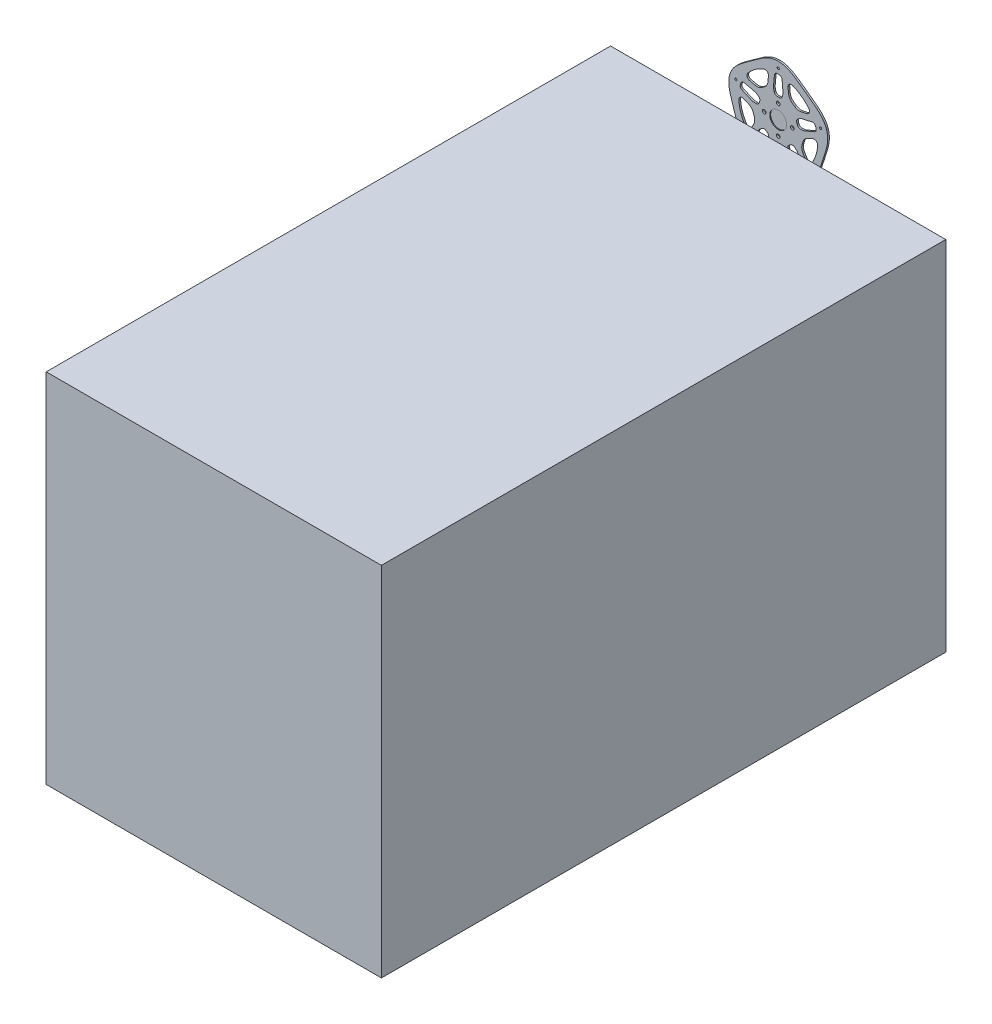
SolidWorks part; units mm, degrees
material "Stop 1060"
ref_plane "Płaszczyzna przednia" through (0, 0, 0) normal (0, 0, 1) x (1, 0, 0)
ref_plane "Płaszczyzna górna" through (0, 0, 0) normal (0, 1, 0) x (1, 0, 0)
ref_plane "Płaszczyzna prawa" through (0, 0, 0) normal (1, 0, 0) x (0, 0, -1)
sketch "Szkic1" plane through (0, 0, 0) normal (0, 0, 1) x (1, 0, 0)
  line L0 (0, 0) -> (51.1373, 70.3845) construction
  line L1 (0, 0) -> (0, 87) construction
  line L42 (64.6668, 37.9895) -> (41.3071, 32.5965)
  line L43 (69.2558, 28.7859) -> (41.6924, 22.4224)
  line L44 (38.6664, 21.1739) -> (30.949, 16.3814)
  line L45 (35.8646, 30.1162) -> (26.2605, 23.1384)
  line L46 (43.7274, 5.5975) -> (34.667, 4.9385)
  line L47 (72.9491, 17.4193) -> (46.9094, 6.3661)
  line L48 (-6.7939, 65.4105) -> (-8.4413, 46.5807)
  line L49 (-8.189, 43.317) -> (-7.2584, 39.5397)
  line L50 (69.805, 5.2211) -> (52.5779, -2.0914)
  line L51 (46.7169, -3.2838) -> (34.8456, -3.2838)
  line L52 (56.1133, -49.7624) -> (43.7657, -29.2126)
  line L53 (-7.4667, 69.6006) -> (-7.4667, 29.102) construction
  line L54 (48.7783, -56.9709) -> (34.2086, -32.7229)
  line L55 (32.0861, -30.2308) -> (25.1434, -24.3721)
  line L56 (39.725, -24.8029) -> (30.1209, -17.8251)
  line L57 (-17.3877, 59.0596) -> (-18.2365, 49.3583)
  line L58 (18.836, -39.8576) -> (15.4095, -31.4442)
  line L59 (39.1092, -63.9958) -> (20.5503, -42.6462)
  line L60 (26.5365, -64.7751) -> (14.2585, -50.6508)
  line L61 (-17.5594, 43.4157) -> (-13.891, 32.1254)
  line L62 (11.3132, -45.4452) -> (7.6448, -34.1549)
  line L63 (-29.9869, -68.7443) -> (-14.2585, -50.6508)
  line L64 (-39.1092, -63.9958) -> (-20.5503, -42.6462)
  line L65 (-18.836, -39.8576) -> (-15.4095, -31.4442)
  line L66 (-11.3132, -45.4452) -> (-7.6448, -34.1549)
  line L67 (-32.0861, -30.2308) -> (-25.1434, -24.3721)
  line L68 (-48.7783, -56.9709) -> (-34.2086, -32.7229)
  line L69 (-53.4046, -45.2543) -> (-43.7657, -29.2126)
  line L70 (-39.725, -24.8029) -> (-30.1209, -17.8251)
  line L71 (-74.6462, 7.2761) -> (-52.5779, -2.0914)
  line L72 (-72.9491, 17.4193) -> (-46.9094, 6.3661)
  line L73 (-43.7274, 5.5975) -> (-34.667, 4.9385)
  line L74 (0, 0) -> (32.9395, 101.3773) construction
  line L111 (-46.7169, -3.2838) -> (-34.8456, -3.2838)
  line L112 (-38.6664, 21.1739) -> (-30.949, 16.3814)
  line L113 (-69.2558, 28.7859) -> (-41.6924, 22.4224)
  line L114 (-59.5423, 36.8064) -> (-41.3071, 32.5965)
  line L115 (-35.8646, 30.1162) -> (-26.2605, 23.1384)
  line L116 (-29.0561, 35.0629) -> (-24.3679, 38.469)
  line L117 (24.3679, 38.469) -> (29.0561, 35.0629)
  line L118 (44.1163, -11.2877) -> (42.3256, -16.799)
  line L119 (2.8975, -45.4452) -> (-2.8975, -45.4452)
  line L120 (17.5594, 43.4157) -> (13.891, 32.1254)
  line L121 (8.189, 43.317) -> (7.2584, 39.5397)
  line L122 (16.6054, 68.0019) -> (18.2365, 49.3583)
  line L123 (5.9758, 74.7616) -> (8.4413, 46.5807)
  line L124 (-42.3256, -16.799) -> (-44.1163, -11.2877)
  circle A0 centre (0, 0) radius 79 construction
  circle A2 centre (0, 0) radius 25 construction
  circle A3 centre (0, 0) radius 3.3
  circle A4 centre (0, 25) radius 3.2
  circle A5 centre (0, 79) radius 1.9
  circle A6 centre (25, 0) radius 3.2
  circle A7 centre (0, -25) radius 3.2
  circle A8 centre (-25, 0) radius 3.2
  circle A9 centre (75.1335, 24.4123) radius 1.9
  circle A10 centre (46.435, -63.9123) radius 1.9
  circle A11 centre (-46.435, -63.9123) radius 1.9
  circle A12 centre (-75.1335, 24.4123) radius 1.9
  circle A13 centre (0, 0) radius 87 construction
  arc A54 (35.8646, 30.1162) -> (41.3071, 32.5965) centre (44.6814, 17.9809) cw
  arc A55 (38.6664, 21.1739) -> (41.6924, 22.4224) centre (43.9419, 12.6787) cw
  arc A56 (43.7274, 5.5975) -> (46.9094, 6.3661) centre (43.0021, 15.5711) ccw
  arc A57 (46.7169, -3.2838) -> (52.5779, -2.0914) centre (46.7169, 11.7162) ccw
  arc A58 (39.725, -24.8029) -> (43.7657, -29.2126) centre (30.9082, -36.9381) cw
  arc A59 (32.0861, -30.2308) -> (34.2086, -32.7229) centre (25.6369, -37.8733) cw
  circle A60 centre (0, 0) radius 70
  arc A61 (-8.189, 43.317) -> (-8.4413, 46.5807) centre (1.5207, 45.7091) cw
  arc A62 (18.836, -39.8576) -> (20.5503, -42.6462) centre (28.0974, -36.0857) ccw
  arc A63 (11.3132, -45.4452) -> (14.2585, -50.6508) centre (25.5791, -40.8099) ccw
  arc A64 (-11.3132, -45.4452) -> (-14.2585, -50.6508) centre (-25.5791, -40.8099) cw
  arc A65 (-18.2391, 49.3276) -> (-18.2365, 49.3583) centre (-3.2936, 48.051) cw
  arc A66 (-18.836, -39.8576) -> (-20.5503, -42.6462) centre (-28.0974, -36.0857) cw
  arc A67 (-32.0861, -30.2308) -> (-34.2086, -32.7229) centre (-25.6369, -37.8733) ccw
  arc A68 (-39.725, -24.8029) -> (-43.7657, -29.2126) centre (-30.9082, -36.9381) ccw
  arc A69 (8.189, 43.317) -> (8.4413, 46.5807) centre (-1.5207, 45.7091) ccw
  arc A70 (-46.7169, -3.2838) -> (-52.5779, -2.0914) centre (-46.7169, 11.7162) cw
  arc A71 (-43.7274, 5.5975) -> (-46.9094, 6.3661) centre (-43.0021, 15.5711) cw
  arc A72 (-38.6664, 21.1739) -> (-41.6924, 22.4224) centre (-43.9419, 12.6787) ccw
  arc A73 (17.5594, 43.4157) -> (18.2365, 49.3583) centre (3.2936, 48.051) ccw
  arc A74 (-41.2772, 32.5895) -> (-41.3071, 32.5965) centre (-44.6814, 17.9809) ccw
  arc A75 (-24.3679, 38.469) -> (-18.2391, 49.3276) centre (-33.1847, 50.6043) ccw
  arc A76 (-41.2772, 32.5895) -> (-29.0561, 35.0629) centre (-37.8729, 47.1981) ccw
  arc A77 (29.0561, 35.0629) -> (41.2772, 32.5895) centre (37.8729, 47.1981) ccw
  arc A78 (18.2391, 49.3276) -> (24.3679, 38.469) centre (33.1847, 50.6043) ccw
  arc A79 (42.3256, -16.799) -> (43.7498, -29.1862) centre (56.5914, -21.4342) ccw
  arc A80 (52.5496, -2.1034) -> (44.1163, -11.2877) centre (58.3822, -15.9229) ccw
  arc A81 (-2.8975, -45.4452) -> (-14.2383, -50.6276) centre (-2.8975, -60.4452) ccw
  arc A82 (14.2383, -50.6276) -> (2.8975, -45.4452) centre (2.8975, -60.4452) ccw
  arc A83 (-44.1163, -11.2877) -> (-52.5496, -2.1034) centre (-58.3822, -15.9229) ccw
  arc A84 (-43.7498, -29.1862) -> (-42.3256, -16.799) centre (-56.5914, -21.4342) ccw
  arc A85 (-7.4667, 69.6006) -> (0, 70) centre (0, 0) ccw
  arc A86 (-1.9524, 69.9728) -> (0, 70) centre (0, 0) cw
  arc A87 (-6.7939, 65.4105) -> (-1.9524, 69.9728) centre (-1.8129, 64.9747) cw
  arc A88 (-25.5554, 65.1684) -> (-59.5423, 36.8064) centre (0, 0) ccw
  arc A89 (-17.3877, 59.0596) -> (-25.5554, 65.1684) centre (-23.3649, 59.5826) ccw
  circle A90 centre (0, 0) radius 35
  arc A91 (17.3877, 59.0596) -> (25.5554, 65.1684) centre (23.3649, 59.5826) cw
  arc A92 (6.7939, 65.4105) -> (1.9524, 69.9728) centre (1.8129, 64.9747) ccw
  arc A93 (61.5421, 1.7137) -> (69.8759, -4.1664) centre (63.8865, -3.8093) cw
  arc A94 (64.3085, 13.7516) -> (67.1514, 19.766) centre (62.3548, 18.3541) ccw
  arc A95 (60.1096, 26.6743) -> (65.9447, 23.4796) centre (61.2344, 21.8025) cw
  arc A96 (50.7959, 34.7871) -> (54.0818, 44.4427) centre (49.4462, 40.6334) ccw
  arc A97 (20.6474, -58.0005) -> (17.6303, -67.7434) centre (16.1192, -61.9368) cw
  arc A98 (32.9509, -56.9116) -> (39.5495, -57.7567) centre (36.7245, -53.6313) ccw
  arc A99 (43.9437, -48.9248) -> (42.7085, -55.4616) centre (39.6579, -51.5) cw
  arc A100 (48.7813, -37.56) -> (58.9798, -37.7013) centre (53.9243, -34.4698) ccw
  arc A101 (-48.7813, -37.56) -> (-58.9798, -37.7013) centre (-53.9243, -34.4698) cw
  arc A102 (-43.9437, -48.9248) -> (-42.7085, -55.4616) centre (-39.6579, -51.5) ccw
  arc A103 (-32.9509, -56.9116) -> (-39.5495, -57.7567) centre (-36.7245, -53.6313) cw
  arc A104 (-20.6474, -58.0005) -> (-17.6303, -67.7434) centre (-16.1192, -61.9368) ccw
  arc A105 (-50.7959, 34.7871) -> (-54.0818, 44.4427) centre (-49.4462, 40.6334) cw
  arc A106 (-60.1096, 26.6743) -> (-65.9447, 23.4796) centre (-61.2344, 21.8025) ccw
  arc A107 (-64.3085, 13.7516) -> (-67.1514, 19.766) centre (-62.3548, 18.3541) cw
  arc A108 (-61.5421, 1.7137) -> (-69.8759, -4.1664) centre (-63.8865, -3.8093) ccw
  arc A109 (-7.4667, 29.102) -> (6.8673, 29.2492) centre (0, 0) ccw
  arc A110 (-1.2229, 34.9786) -> (1.2229, 34.9786) centre (0, 0) cw
  arc A111 (-7.2584, 39.5397) -> (-1.2229, 34.9786) centre (-1.4326, 40.975) ccw
  arc A112 (7.2584, 39.5397) -> (1.2229, 34.9786) centre (1.4326, 40.975) cw
  arc A113 (35.3615, 19.1216) -> (32.8887, 11.9721) centre (38.5268, 14.0244) ccw
  arc A114 (39.8474, 5.3153) -> (33.6446, 9.6459) centre (39.4122, 11.2995) cw
  arc A115 (29.113, -27.7219) -> (21.5493, -27.5795) centre (25.2435, -32.3074) ccw
  arc A116 (17.3687, -36.2546) -> (19.5705, -29.0171) centre (22.9255, -33.9915) cw
  arc A117 (-17.3687, -36.2546) -> (-19.5705, -29.0171) centre (-22.9255, -33.9915) ccw
  arc A118 (-29.113, -27.7219) -> (-21.5493, -27.5795) centre (-25.2435, -32.3074) cw
  arc A119 (-39.8474, 5.3153) -> (-33.6446, 9.6459) centre (-39.4122, 11.2995) ccw
  arc A120 (-35.3615, 19.1216) -> (-32.8887, 11.9721) centre (-38.5268, 14.0244) cw
  spline S0 degree 3 poles (0, 87) (18.2248, 86.9986) (32.2889, 73.5369) (46.435, 63.9123) knots 0 0 0 0 1 1 1 1 construction
  spline S1 degree 3 poles (82.7419, 26.8845) (77.1088, 44.2169) (59.9599, 53.4327) (46.435, 63.9123) knots 0 0 0 0 1 1 1 1 construction
  spline S2 degree 3 poles (82.7419, 26.8845) (88.3724, 9.5512) (79.9156, -7.9844) (75.1335, -24.4123) knots 0 0 0 0 1 1 1 1 construction
  spline S3 degree 3 poles (51.1373, -70.3845) (65.8807, -59.6711) (69.3462, -40.5137) (75.1335, -24.4123) knots 0 0 0 0 1 1 1 1 construction
  spline S4 degree 3 poles (51.1373, -70.3845) (36.3923, -81.0957) (17.1016, -78.4715) (0, -79) knots 0 0 0 0 1 1 1 1 construction
  spline S5 degree 3 poles (-51.1373, -70.3845) (-36.3923, -81.0957) (-17.1016, -78.4715) (0, -79) knots 0 0 0 0 1 1 1 1 construction
  spline S6 degree 3 poles (-51.1373, -70.3845) (-65.8807, -59.6711) (-69.3462, -40.5137) (-75.1335, -24.4123) knots 0 0 0 0 1 1 1 1 construction
  spline S7 degree 3 poles (-82.7419, 26.8845) (-88.3724, 9.5512) (-79.9156, -7.9844) (-75.1335, -24.4123) knots 0 0 0 0 1 1 1 1 construction
  spline S8 degree 3 poles (-82.7419, 26.8845) (-77.1088, 44.2169) (-59.9599, 53.4327) (-46.435, 63.9123) knots 0 0 0 0 1 1 1 1 construction
  spline S9 degree 3 poles (0, 87) (-18.2248, 86.9986) (-32.2889, 73.5369) (-46.435, 63.9123) knots 0 0 0 0 1 1 1 1 construction
  spline S10 degree 1 poles (0, 90) (48.1992, 66.3406) knots 0 0 1 1 construction
  spline S11 degree 1 poles (85.5951, 27.8115) (48.1992, 66.3406) knots 0 0 1 1 construction
  spline S12 degree 1 poles (85.5951, 27.8115) (77.988, -25.3398) knots 0 0 1 1 construction
  spline S13 degree 1 poles (52.9007, -72.8115) (77.988, -25.3398) knots 0 0 1 1 construction
  spline S14 degree 1 poles (52.9007, -72.8115) (0, -82.0014) knots 0 0 1 1 construction
  spline S15 degree 1 poles (-52.9007, -72.8115) (0, -82.0014) knots 0 0 1 1 construction
  spline S16 degree 1 poles (-52.9007, -72.8115) (-77.988, -25.3398) knots 0 0 1 1 construction
  spline S17 degree 1 poles (-85.5951, 27.8115) (-77.988, -25.3398) knots 0 0 1 1 construction
  spline S18 degree 1 poles (-85.5951, 27.8115) (-48.1992, 66.3406) knots 0 0 1 1 construction
  spline S19 degree 1 poles (0, 90) (-48.1992, 66.3406) knots 0 0 1 1 construction
  spline S20 degree 3 poles (0, 90) (1.2173, 89.9999) (3.6733, 89.8856) (8.3842, 89.2383) (14.0239, 87.7208) (20.3782, 85.0183) (26.3875, 81.6762) (32.115, 77.9195) (37.6265, 73.9608) (42.0815, 70.6707) (45.5966, 68.1385) (47.3232, 66.9366) (48.1992, 66.3406) knots -0.000004 -0.000004 -0.000004 -0.000004 0.062609 0.125222 0.250448 0.375675 0.500901 0.626127 0.751353 0.87658 0.939193 1.001806 1.001806 1.001806 1.001806
  spline S21 degree 3 poles (48.1992, 66.3406) (49.0368, 65.6916) (50.7135, 64.4209) (54.2079, 61.8604) (58.7136, 58.6401) (64.1818, 54.6216) (69.5245, 50.3354) (74.56, 45.6529) (79.0938, 40.4447) (82.2798, 35.55) (84.3511, 31.2697) (85.2188, 28.9693) (85.5951, 27.8115) knots -0.000004 -0.000004 -0.000004 -0.000004 0.062609 0.125222 0.250448 0.375675 0.500901 0.626127 0.751353 0.87658 0.939193 1.001806 1.001806 1.001806 1.001806
  spline S22 degree 3 poles (85.5951, 27.8115) (85.9712, 26.6537) (86.6214, 24.2826) (87.4616, 19.6023) (87.761, 13.7697) (87.1544, 6.8913) (85.8329, 0.1433) (84.03, -6.4647) (81.9681, -12.9298) (80.2157, -18.1835) (78.8937, -22.3089) (78.2841, -24.3225) (77.988, -25.3398) knots -0.000004 -0.000004 -0.000004 -0.000004 0.062609 0.125222 0.250448 0.375675 0.500901 0.626127 0.751353 0.87658 0.939193 1.001806 1.001806 1.001806 1.001806
  spline S23 degree 3 poles (77.988, -25.3398) (77.6296, -26.337) (76.9392, -28.3242) (75.5838, -32.4389) (73.9136, -37.7192) (71.7815, -44.1615) (69.356, -50.5673) (66.4588, -56.8033) (62.9065, -62.7246) (59.236, -67.2672) (55.8052, -70.5598) (53.8855, -72.0959) (52.9007, -72.8115) knots -0.000004 -0.000004 -0.000004 -0.000004 0.062609 0.125222 0.250448 0.375675 0.500901 0.626127 0.751353 0.87658 0.939193 1.001806 1.001806 1.001806 1.001806
  spline S24 degree 3 poles (52.9007, -72.8115) (51.9158, -73.527) (49.8616, -74.8781) (45.67, -77.1235) (40.2154, -79.2106) (33.4862, -80.7592) (26.6601, -81.5876) (19.8184, -81.9149) (13.0325, -81.9518) (7.4945, -81.9087) (3.1624, -81.9262) (1.0591, -81.9687) (0, -82.0014) knots -0.000004 -0.000004 -0.000004 -0.000004 0.062609 0.125222 0.250448 0.375675 0.500901 0.626127 0.751353 0.87658 0.939193 1.001806 1.001806 1.001806 1.001806
  spline S25 degree 3 poles (0, -82.0014) (-1.0591, -81.9687) (-3.1624, -81.9262) (-7.4945, -81.9087) (-13.0325, -81.9518) (-19.8184, -81.9149) (-26.6601, -81.5876) (-33.4862, -80.7592) (-40.2154, -79.2106) (-45.67, -77.1235) (-49.8616, -74.8781) (-51.9158, -73.527) (-52.9007, -72.8115) knots -0.000004 -0.000004 -0.000004 -0.000004 0.062609 0.125222 0.250448 0.375675 0.500901 0.626127 0.751353 0.87658 0.939193 1.001806 1.001806 1.001806 1.001806
  spline S26 degree 3 poles (-52.9007, -72.8115) (-53.8855, -72.0959) (-55.8052, -70.5598) (-59.236, -67.2672) (-62.9065, -62.7246) (-66.4588, -56.8033) (-69.356, -50.5673) (-71.7815, -44.1615) (-73.9136, -37.7192) (-75.5838, -32.4389) (-76.9392, -28.3242) (-77.6296, -26.337) (-77.988, -25.3398) knots -0.000004 -0.000004 -0.000004 -0.000004 0.062609 0.125222 0.250448 0.375675 0.500901 0.626127 0.751353 0.87658 0.939193 1.001806 1.001806 1.001806 1.001806
  spline S27 degree 3 poles (-77.988, -25.3398) (-78.2841, -24.3225) (-78.8937, -22.3089) (-80.2157, -18.1835) (-81.9681, -12.9298) (-84.03, -6.4647) (-85.8329, 0.1433) (-87.1544, 6.8913) (-87.761, 13.7697) (-87.4616, 19.6023) (-86.6214, 24.2826) (-85.9712, 26.6537) (-85.5951, 27.8115) knots -0.000004 -0.000004 -0.000004 -0.000004 0.062609 0.125222 0.250448 0.375675 0.500901 0.626127 0.751353 0.87658 0.939193 1.001806 1.001806 1.001806 1.001806
  spline S28 degree 3 poles (-85.5951, 27.8115) (-85.2188, 28.9693) (-84.3511, 31.2697) (-82.2798, 35.55) (-79.0938, 40.4447) (-74.56, 45.6529) (-69.5245, 50.3354) (-64.1818, 54.6216) (-58.7136, 58.6401) (-54.2079, 61.8604) (-50.7135, 64.4209) (-49.0368, 65.6916) (-48.1992, 66.3406) knots -0.000004 -0.000004 -0.000004 -0.000004 0.062609 0.125222 0.250448 0.375675 0.500901 0.626127 0.751353 0.87658 0.939193 1.001806 1.001806 1.001806 1.001806
  spline S29 degree 3 poles (-48.1992, 66.3406) (-47.3232, 66.9366) (-45.5966, 68.1385) (-42.0815, 70.6707) (-37.6265, 73.9608) (-32.115, 77.9195) (-26.3875, 81.6762) (-20.3782, 85.0183) (-14.0239, 87.7208) (-8.3842, 89.2383) (-3.6733, 89.8856) (-1.2173, 89.9999) (0, 90) knots -0.000004 -0.000004 -0.000004 -0.000004 0.062609 0.125222 0.250448 0.375675 0.500901 0.626127 0.751353 0.87658 0.939193 1.001806 1.001806 1.001806 1.001806
  point P18 (0, 0)
  point P27 (0, 0)
  point P64 (0, 0)
  point P72 (-8.5859, 44.9279)
  point P166 (0, 0)
  point P188 (0.227, 0)
  point P198 (0, 0)
  point P260 (0, 0)
  point P291 (0, 0)
  point P369 (0.5409, 0.0601)
  dimension "D1" = 158
  dimension "D2" = 6.6
  dimension "D3" = 50
  dimension "D4" = 3.8
  dimension "D5" = 6.4
  dimension "D8" = 174
  dimension "D13" = 5
  dimension "D14" = 6
  dimension "D15" = 10
  dimension "D10" = 70
  dimension "D11" = 140
  dimension "D16" = 10
  dimension "D18" = 15
  dimension "D23" = 15
  dimension "D26" = 6
  dimension "D27" = 6
  dimension "D29" = 70
  dimension "D9" = 36
  dimension "D12" = 5
  dimension "D17" = 18
  dimension "D20" = 5
  dimension "D21" = 11.8713
  dimension "D22" = 18
  dimension "D19" = 3
  dimension "D6" = 4
  dimension "D7" = 5
  dimension "D24" = 5
  dimension "D25" = 5
  dimension "D28" = 5
extrude "Dodanie-wyciągnięcie1" add sketch "Szkic1" along normal blind 3 contours S29 S28 S27 S26 S25 S24 S23 S22 S21 S20 A60 A85 | A119 L73 A71 L72 A60 L71 A70 L111 A90 | A120 A90 A111 L49 A61 L48 A87 A60 A89 L57 A65 A75 L116 A76 A74 L114 L113 A72 L112 | L121 A112 A90 L120 A73 L122 A60 L123 A69 | A90 L45 A54 A77 L117 A78 A73 L120 | A113 L44 A55 L43 A60 L42 A54 L45 A90 | A114 A90 L51 A57 L50 A60 L47 A56 L46 | A90 L56 A58 A79 L118 A80 A57 L51 | A115 L55 A59 L54 A60 L52 A58 L56 A90 | A116 A90 L62 A63 L60 A60 L59 A62 L58 | A90 L66 A64 A81 L119 A82 A63 L62 | A117 L65 A66 L64 A60 L63 A64 L66 A90 | A118 A90 L70 A68 L69 A60 L68 A67 L67 | A90 L111 A70 A83 L124 A84 A68 L70 | A108 L71 A60 | L72 A107 A60 | L114 A105 A88 | A106 L113 A60 | A90 A3 A4 A6 A7 A8 | A3 | A92 L123 A60 | L122 A91 A85 | A96 L42 A60 | L43 A95 A60 | A94 L47 A60 | L50 A93 A85 | A100 L52 A60 | L54 A99 A60 | A98 L59 A60 | L60 A97 A85 | A104 L63 A60 | L64 A103 A60 | A102 L68 A60 | L69 A101 A85 region at (45.1515, 27.4698, 0) region at (56.2442, 38.1885, 0) region at (24.0486, 33.1001, 0) region at (63.7725, 26.5292, 0) region at (18.939, 65.2923, 0) region at (12.1727, 51.4302, 0) region at (29.2457, 17.36, 0) region at (67.1865, 16.0219, 0) region at (5.524, 68.8492, 0) region at (52.6746, 4.3159, 0) region at (67.9492, 2.1644, 0) region at (-7.8787, 34.9807, 0) region at (38.9115, -12.6431, 0) region at (40.0779, -34.453, 0) region at (53.6998, -41.6905, 0) region at (-56.2442, 38.1885, 0) region at (20.382, -48.7629, 0) region at (-52.6746, 4.3159, 0) region at (44.9375, -52.4532, 0) region at (0, -40.914, 0) region at (-38.9115, -12.6431, 0) region at (-63.7725, 26.5292, 0) region at (-20.382, -48.7629, 0) region at (-40.0779, -34.453, 0) region at (35.9995, -58.9471, 0) region at (-67.1865, 16.0219, 0) region at (23.0559, -63.9546, 0) region at (-67.9492, 2.1644, 0) region at (-23.0559, -63.9546, 0) region at (-53.6998, -41.6905, 0) region at (-35.9995, -58.9471, 0) region at (-44.9375, -52.4532, 0) region at (0, 0, 0) region at (24.5128, 79.8404, 0)
sketch "Szkic2" plane through (0, 0, 3) normal (0, 0, 1) x (1, 0, 0)
  circle A0 centre (0, 0) radius 15
  dimension "D1" = 30
extrude "Wytnij-wyciągnięcie1" cut sketch "Szkic2" against normal blind 1.5
ref_plane "Płaszczyzna1" through (0, 0, 3.1) normal (0, 0, 1) x (1, 0, 0)
sketch "Szkic3" plane through (0, 0, 3.1) normal (0, 0, 1) x (1, 0, 0)
  line L1 (-296.9479, -668.4565) -> (296.9479, -668.4565)
  line L2 (-296.9479, -668.4565) -> (-296.9479, -35.2062)
  line L3 (-296.9479, -35.2062) -> (296.9479, -35.2062)
  line L4 (296.9479, -668.4565) -> (296.9479, -35.2062)
  line L5 (0, -35.2062) -> (0, -668.4565) construction
  line L6 (-296.9479, -351.8314) -> (296.9479, -351.8314) construction
  point P0 (0, -351.8314)
extrude "Dodanie-wyciągnięcie2" add sketch "Szkic3" along normal blind 1000 separate body
sketch "Sketch1" plane through (0, 0, 0) normal (0, 0, -1) x (-1, 0, 0)
  line L0 (0, 0) -> (-16.4631, 16.4631) construction
  line L1 (0, 0) -> (14.4362, 0) construction
  circle A0 centre (0, 0) radius 25 construction
  circle A1 centre (-17.6777, 17.6777) radius 2.15
  circle A2 centre (17.6777, 17.6777) radius 2.15
  circle A3 centre (17.6777, -17.6777) radius 2.15
  circle A4 centre (-17.6777, -17.6777) radius 2.15
  point P17 (0, 0)
  dimension "D1" = 135
  dimension "D2" = 4.3
  dimension "D3" = 4
extrude "Cut-Extrude1" [suppressed] cut sketch "Sketch1" against normal blind 7
sketch "Sketch2" plane through (0, 0, 3) normal (0, 0, 1) x (1, 0, 0)
  line L1 (-5.15, 2.9734) -> (-5.15, -2.9734)
  line L2 (-5.15, -2.9734) -> (0, -5.9467)
  line L3 (0, -5.9467) -> (5.15, -2.9734)
  line L4 (5.15, -2.9734) -> (5.15, 2.9734)
  line L5 (5.15, 2.9734) -> (0, 5.9467)
  line L6 (0, 5.9467) -> (-5.15, 2.9734)
  circle A0 centre (0, 0) radius 5.15 construction
  dimension "D1" = 10.3
extrude "Cut-Extrude2" [suppressed] cut sketch "Sketch2" against normal blind 5.5
